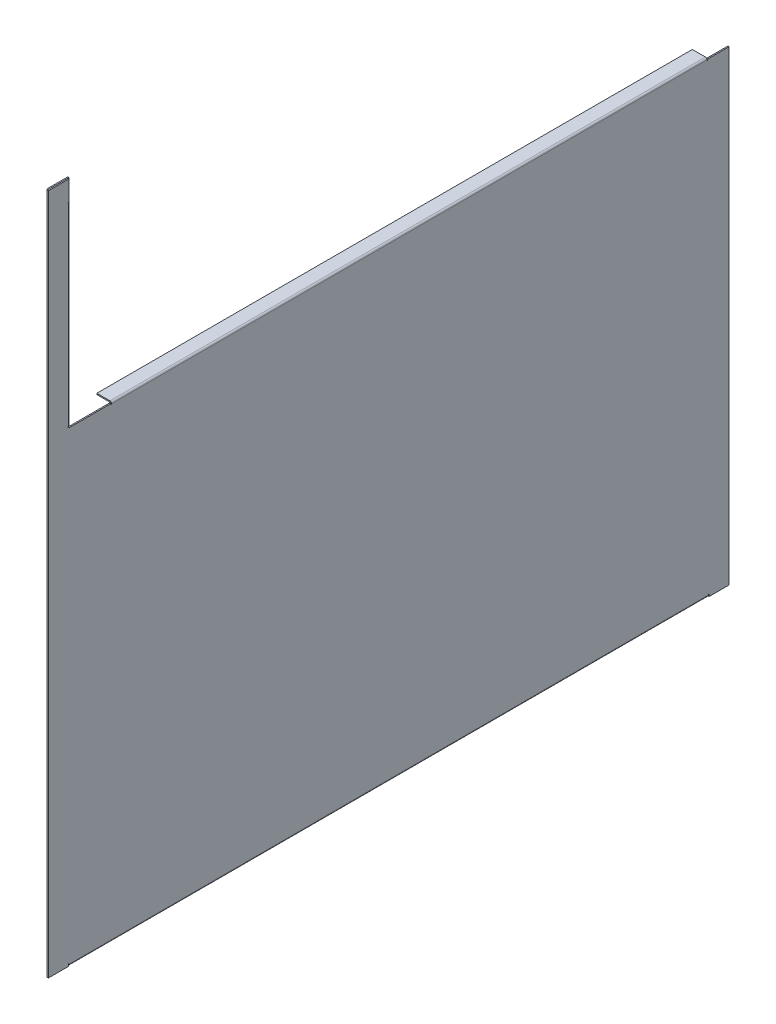
SolidWorks part; units mm, degrees
note: The reader was unsure of these and kept them because the rebuilt part matched: flange length of "Edge-Flange5", "Edge-Flange6", "Edge-Flange8", "Edge-Flange9".
ref_plane "Front Plane" through (0, 0, 0) normal (0, 0, 1) x (1, 0, 0)
ref_plane "Top Plane" through (0, 0, 0) normal (0, 1, 0) x (1, 0, 0)
ref_plane "Right Plane" through (0, 0, 0) normal (1, 0, 0) x (0, 0, -1)
sketch "Sketch10" plane through (0, 0, 0) normal (1, 0, 0) x (0, 0, -1)
  line L0 (-470.9, 501) -> (-470.9, 184.3)
  line L2 (-470.9, 184.3) -> (499, 184.3)
  line L3 (184.3, 184.3) -> (-492.5, -492.5) construction
  line L8 (499, -500.7) -> (499, 184.3)
  line L9 (499, -500.7) -> (-501, -500.7)
  line L10 (-501, -500.7) -> (-501, 501)
  line L11 (-470.9, 501) -> (-501, 501)
  line L12 (492.5, -492.5) -> (-492.5, 492.5) construction
  point P0 (0, 0)
  point P6 (0, 0)
  dimension "D1" = 1000
  dimension "D2" = 1001.7
base flange "Base-Flange2" sketch "Sketch10" thickness 1.7366 reverse thickness direction no parameters "D1"=0.7366
edge flange "Edge-Flange5" sketch "Sketch34" flange angle 90 flange length 30 flange position material inside bend radius 0.7366 thickness 1.7366 relief rectangular parameters "D6"=10
bend "EdgeBend9" bend radius 0.7366 bend angle 90 parameters "D5"=4
sketch "Sketch34" plane through (-1.7366, -500.7, 0) normal (0, -1, 0) x (0, 0, 1)
  line L0 (501, 0) -> (-499, 0) construction
  line L1 (470.8, 0) -> (-468.8, 0)
  line L2 (-468.8, 0) -> (-468.8, 28.2634)
  line L3 (-468.8, 28.2634) -> (470.8, 28.2634)
  line L4 (470.8, 28.2634) -> (470.8, 0)
  dimension "D1" = 30.2
  dimension "D2" = 30.2
edge flange "Edge-Flange6" sketch "Sketch37" flange angle 90 flange length 31.9366 flange position material outside bend radius 0.7366 thickness 1.7366 relief rectangular parameters "D6"=10
sketch "Sketch37" plane through (-1.7366, 0, 470.9) normal (0, 0, -1) x (0, -1, 0)
  line L0 (-184.3, 0) -> (-501, 0) construction
  line L1 (-186.3, 0) -> (-470.8, 0)
  line L2 (-470.8, 0) -> (-470.8, 30.2)
  line L3 (-470.8, 30.2) -> (-186.3, 30.2)
  line L4 (-186.3, 30.2) -> (-186.3, 0)
  dimension "D1" = 30.2
  dimension "D2" = 30.2
  dimension "D3" = 2
bend "EdgeBend10" bend radius 0.7366 bend angle 90 parameters "D5"=5
edge flange "Edge-Flange8" sketch "Sketch43" flange angle 90 flange length 21.7366 flange position material outside bend radius 0.7366 thickness 1.7366 relief rectangular parameters "D6"=10
sketch "Sketch43" plane through (-1.7366, 184.3, 0) normal (0, 1, 0) x (0, 0, -1)
  line L0 (499, 0) -> (-470.9, 0) construction
  line L1 (466.8, 0) -> (-408.1634, 0)
  line L2 (-408.1634, 0) -> (-408.1634, 20)
  line L3 (-408.1634, 20) -> (466.8, 20)
  line L4 (466.8, 20) -> (466.8, 0)
  line L5 (-469.1634, 0.7366) -> (-469.1634, 30.2) construction
  dimension "D1" = 61
  dimension "D2" = 20
  dimension "D3" = 32.2
bend "EdgeBend12" bend radius 0.7366 bend angle 90 parameters "D5"=6
edge flange "Edge-Flange9" sketch "Sketch46" flange angle 90 flange length 31.9366 flange position material outside bend radius 0.7366 thickness 1.7366 relief rectangular parameters "D6"=10
sketch "Sketch46" plane through (-31.9366, 0, 469.1634) normal (-1, 0, 0) x (0, 1, 0)
  line L0 (186.3, 0) -> (470.8, 0) construction
  line L1 (186.4366, 0) -> (470.8, 0)
  line L2 (186.4366, 0) -> (186.4366, 30.2)
  line L3 (186.4366, 30.2) -> (470.8, 30.2)
  line L4 (470.8, 30.2) -> (470.8, 0)
  line L5 (186.0366, 935.9634) -> (186.0366, 61) construction
  dimension "D1" = 30.2
  dimension "D2" = 0.4
bend "EdgeBend13" bend radius 0.7366 bend angle 90 parameters "D5"=7
sketch "Bend-Lines3" [suppressed] plane through (0, 0, 0) normal (0, 1, 0) x (1, 0, 0)
sketch "Bounding-Box3" [suppressed] plane through (0, 0, 0) normal (0, 1, 0) x (1, 0, 0)
sheet metal parameters "Sheet-Metal3" thickness 1.7366 parameters "D1"=0.7366
flat pattern "Flat-Pattern3" [suppressed]
sketch "Bend-Lines4" plane through (0, 0, 0) normal (0, 1, 0) x (1, 0, 0)
sketch3d "Bounding-Box4" [suppressed]
  line L0 (501, -501, 0) -> (-501, -501, 0) construction
  line L1 (501, 501, 0) -> (-501, 501, 0) construction
  line L2 (501, -501, 0) -> (501, 501, 0) construction
  line L3 (-501, -501, 0) -> (-501, 501, 0) construction
sheet metal parameters "Sheet-Metal7" thickness 1.7366 parameters "D1"=0.7366
flat pattern "Flat-Pattern3"
sketch "Bend-Lines4" plane through (0, 0, 0) normal (1, 0, 0) x (0, 0, -1)
  line L8 (-470.8, -499.4873) -> (470.8, -499.4873) construction
  line L12 (-470.8, -499.4873) -> (470.8, -499.4873) construction
  point P14 (-501.5239, 470.5)
  point P15 (-501.5239, 185.5)
sketch3d "Bounding-Box4" [suppressed]
  line L0 (-501, 501, 0) -> (-501, -528.2746, 0) construction
  line L1 (501, 501, 0) -> (501, -528.2746, 0) construction
  line L2 (-501, 501, 0) -> (501, 501, 0) construction
  line L3 (-501, -528.2746, 0) -> (501, -528.2746, 0) construction
bend of the flat pattern "Flatten-<EdgeBend9>1"
sheet metal parameters "Sheet-Metal8" thickness 1.7366 parameters "D1"=0.7366
flat pattern "Flat-Pattern3"
sketch "Bend-Lines4" plane through (0, 0, 0) normal (1, 0, 0) x (0, 0, -1)
  line L0 (-470.3761, 184.3) -> (-470.3761, 497.8) construction
  line L1 (-470.3761, 184.3) -> (-470.3761, 497.8) construction
  line L8 (-470.8, -499.4873) -> (470.8, -499.4873) construction
  line L12 (-470.8, -499.4873) -> (470.8, -499.4873) construction
sketch3d "Bounding-Box4" [suppressed]
  line L0 (-501, 501, 0) -> (-501, -528.2746, 0) construction
  line L1 (501, 501, 0) -> (501, -528.2746, 0) construction
  line L2 (-501, 501, 0) -> (501, 501, 0) construction
  line L3 (-501, -528.2746, 0) -> (501, -528.2746, 0) construction
bend of the flat pattern "Flatten-<EdgeBend9>1"
bend of the flat pattern "Flatten-<EdgeBend10>1"
sheet metal parameters "Sheet-Metal10" thickness 1.7366 parameters "D1"=0.7366
flat pattern "Flat-Pattern3"
sketch "Bend-Lines4" plane through (0, 0, 0) normal (1, 0, 0) x (0, 0, -1)
  line L0 (-470.3761, 184.3) -> (-470.3761, 497.8) construction
  line L1 (-470.3761, 184.3) -> (-470.3761, 497.8) construction
  line L2 (470.8, 184.8239) -> (-468.1634, 184.8239) construction
  line L3 (470.8, 184.8239) -> (-468.1634, 184.8239) construction
  line L8 (-470.8, -499.4873) -> (470.8, -499.4873) construction
  line L12 (-470.8, -499.4873) -> (470.8, -499.4873) construction
sketch3d "Bounding-Box4" [suppressed]
  line L0 (-501, 501, 0) -> (-501, -528.2746, 0) construction
  line L1 (501, 501, 0) -> (501, -528.2746, 0) construction
  line L2 (-501, 501, 0) -> (501, 501, 0) construction
  line L3 (-501, -528.2746, 0) -> (501, -528.2746, 0) construction
bend of the flat pattern "Flatten-<EdgeBend9>1"
bend of the flat pattern "Flatten-<EdgeBend10>1"
bend of the flat pattern "Flatten-<EdgeBend12>1"
sheet metal parameters "Sheet-Metal11" thickness 1.7366 parameters "D1"=0.7366
flat pattern "Flat-Pattern3"
sketch "Bend-Lines4" plane through (0, 0, 0) normal (1, 0, 0) x (0, 0, -1)
  line L0 (-470.3761, 186.3) -> (-470.3761, 470.8) construction
  line L1 (-470.3761, 186.3) -> (-470.3761, 470.8) construction
  line L2 (466.8, 184.8239) -> (-408.1634, 184.8239) construction
  line L3 (466.8, 184.8239) -> (-408.1634, 184.8239) construction
  line L4 (-439.1283, 186.4366) -> (-439.1283, 470.8) construction
  line L5 (-439.1283, 186.4366) -> (-439.1283, 470.8) construction
  line L8 (-470.8, -499.4873) -> (468.8, -499.4873) construction
  line L12 (-470.8, -499.4873) -> (468.8, -499.4873) construction
sketch3d "Bounding-Box4" [suppressed]
  line L0 (-501, 501, 0) -> (-501, -528.2746, 0) construction
  line L1 (499, 501, 0) -> (499, -528.2746, 0) construction
  line L2 (-501, 501, 0) -> (499, 501, 0) construction
  line L3 (-501, -528.2746, 0) -> (499, -528.2746, 0) construction
bend of the flat pattern "Flatten-<EdgeBend9>1"
bend of the flat pattern "Flatten-<EdgeBend10>1"
bend of the flat pattern "Flatten-<EdgeBend12>1"
bend of the flat pattern "Flatten-<EdgeBend13>1"
